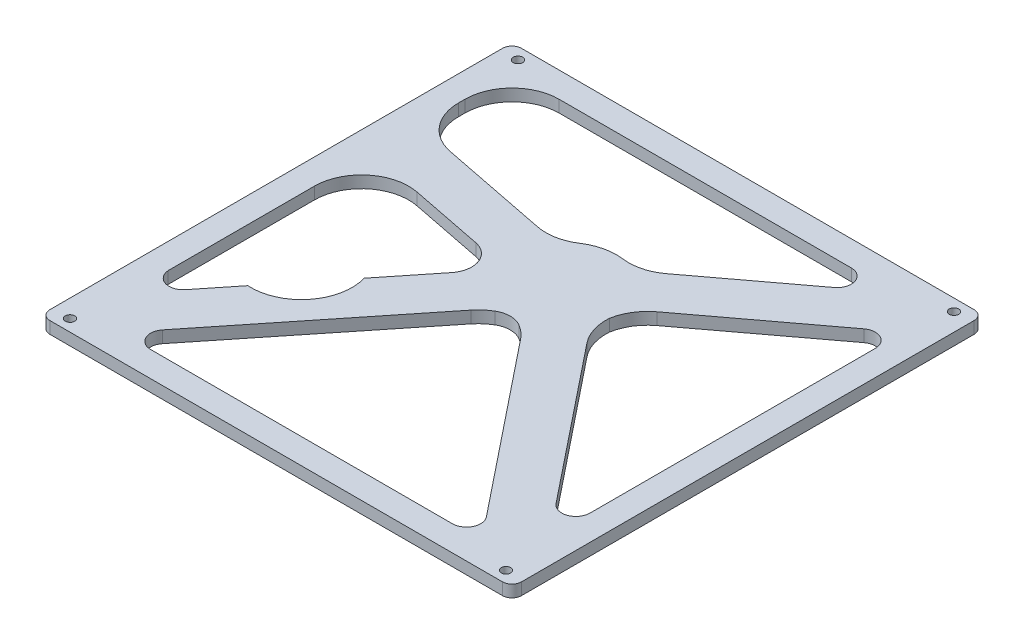
SolidWorks part; units mm, degrees
material "1060 Alloy"
ref_plane "Front Plane" through (0, 0, 0) normal (0, 0, 1) x (1, 0, 0)
ref_plane "Top Plane" through (0, 0, 0) normal (0, 1, 0) x (1, 0, 0)
ref_plane "Right Plane" through (0, 0, 0) normal (1, 0, 0) x (0, 0, -1)
ref_plane "Plane1" through (0, 0, 0) normal (0, -1, 0) x (1, 0, 0)
sketch "Sketch1" plane through (0, 0, 0) normal (0, -1, 0) x (1, 0, 0)
  line L0 (-50, -50) -> (50, -50)
  line L1 (50, -50) -> (50, 50)
  line L2 (50, 50) -> (-50, 50)
  line L3 (-50, 50) -> (-50, -50)
extrude "Boss-Extrude1" add sketch "Sketch1" against normal blind 2.54
fillet "Fillet1" radius 2 4 edges at (-50, 1.27, -50) (-50, 1.27, 50) (50, 1.27, -50) (50, 1.27, 50) tangent propagation no
sketch "Sketch2" plane through (0, 2.54, 0) normal (0, 1, 0) x (1, 0, 0)
  line L0 (0, 0) -> (0, 50) construction
  line L1 (-50, -47.5) -> (-50, -50) construction
  line L2 (-47.5, -50) -> (-50, -50) construction
  line L3 (-47.5, 50) -> (-50, 50) construction
  line L4 (50, 47.5) -> (50, 50) construction
  line L5 (47.5, 50) -> (50, 50) construction
  line L6 (47.5, -50) -> (50, -50) construction
  line L7 (50, -47.5) -> (50, -50) construction
  line L8 (-50, 47.5) -> (-50, 50) construction
  circle A0 centre (-46.23, -47.5) radius 1
  circle A1 centre (-46.23, 47.5) radius 1
  circle A2 centre (46.23, 47.5) radius 1
  circle A3 centre (46.23, -47.5) radius 1
  point P25 (0, 0)
sketch "Sketch5" plane through (0, 2.54, 0) normal (0, 1, 0) x (1, 0, 0)
  line L4 (-34.3633, 44.6388) -> (27.3056, 44.6388)
  line L9 (44.6388, 32.3888) -> (44.6388, -28.0827)
  line L14 (31.9938, -44.6388) -> (-34.3633, -44.6388)
  line L19 (-44.6332, -34.3677) -> (-44.6332, 34.3588)
  line L20 (0, 11.1593) -> (44.6388, 44.6388) construction
  line L21 (50, -34.3633) -> (50, -50) construction
  line L22 (44.6388, -36.635) -> (44.6388, -44.6388)
  line L23 (44.6388, -44.6388) -> (38.2357, -44.6388)
  line L24 (-34.3633, -44.6388) -> (-44.6332, -44.6388)
  line L25 (-44.6332, -44.6388) -> (-44.6332, -34.3677)
  line L26 (-44.6332, 34.3588) -> (-44.6332, 44.6388)
  line L27 (-44.6332, 44.6388) -> (-34.3633, 44.6388)
  line L28 (36.3056, 44.6388) -> (44.6388, 44.6388)
  line L29 (44.6388, 44.6388) -> (44.6388, 38.3888)
  line L30 (0, 0) -> (0, 11.1593) construction
  line L31 (0, 11.1593) -> (44.6388, -44.6388) construction
  line L32 (-2.2164, 0.3849) -> (-34.3364, -39.7647)
  line L33 (-39.2962, -29.9567) -> (-10.0251, 6.6319)
  line L34 (39.2962, -29.9567) -> (10.0251, 6.6319)
  line L35 (2.2164, 0.3849) -> (34.3364, -39.7647)
  line L36 (29.1056, 39.2388) -> (4.8383, 21.0381)
  line L37 (10.8384, 13.0382) -> (39.8388, 34.7887)
  line L38 (-44.6388, 32.3888) -> (-44.6388, -28.0827)
  line L39 (0, 11.1593) -> (-44.5603, 19.9808) construction
  line L44 (-8.6439, 17.9624) -> (-44.6332, 25.0871)
  line L45 (-10.5824, 8.1573) -> (-44.6388, 14.8993)
  circle A20 centre (0, 11.1593) radius 11
  arc A21 (31.9938, -44.6388) -> (34.3364, -39.7647) centre (31.9938, -41.6388) ccw
  arc A22 (44.6388, -28.0827) -> (39.2962, -29.9567) centre (41.6388, -28.0827) cw
  arc A23 (44.6388, 32.3888) -> (39.8388, 34.7887) centre (41.6388, 32.3888) ccw
  arc A24 (27.3056, 44.6388) -> (29.1056, 39.2388) centre (27.3056, 41.6388) cw
  arc A26 (-31.9938, -44.6388) -> (-34.3364, -39.7647) centre (-31.9938, -41.6388) cw
  arc A27 (-44.6388, -28.0827) -> (-39.2962, -29.9567) centre (-41.6388, -28.0827) ccw
  circle A29 centre (-32.7578, -11.8935) radius 10.7389
  point P3 (2.2164, 0.3849)
  point P4 (38.2357, -44.6388)
  point P6 (0, 0)
  point P8 (0, 0)
  point P13 (10.0251, 6.6319)
  point P14 (44.6388, -36.635)
  point P18 (-10.5824, 8.1573)
  point P19 (4.8383, 21.0381)
  point P22 (10.8384, 13.0382)
  point P23 (44.6388, 38.3888)
  point P24 (36.3056, 44.6388)
  point P30 (0, 0)
  point P44 (0, 0)
  point P45 (-8.6404, 17.9669)
  dimension "D1" = 3
extrude "Cut-Extrude1" cut sketch "Sketch5" against normal blind 10 contours L19 A27 L33 A20 | A26 L14 A21 L35 A20 L32 | L9 A23 L37 A20 L34 A22 | L4 A20 L36 A24 | L33 A29 | L33 A29 region at (-11.2055, 2.54, -33.7989) region at (32.1629, 2.54, -4.1478) region at (-31.9742, 2.54, 0.7025) region at (0, 2.54, 28.6798) region at (-26.4793, 2.54, 16.9164) region at (-33.9103, 2.54, 10.9716)
extrude "Cut-Extrude2" cut sketch "Sketch2" against normal blind 10
fillet "Fillet2" radius 10 11 edges at (-10.0251, 1.27, -6.6319) (4.8383, 1.27, -21.0381) (10.8384, 1.27, -13.0382) (10.0251, 1.27, -6.6319) (-2.2164, 1.27, -0.3849) (2.2164, 1.27, -0.3849) (-10.5824, 1.27, -8.1573) (-8.6439, 1.27, -17.9624) (-44.6332, 1.27, -14.8982) (-44.6332, 1.27, -25.0871) (-44.6332, 1.27, -44.6388)
fillet "Fillet3" radius 5 2 edges at (0, 1.27, 0.0133) (-11.085, 1.27, -7.1091)
